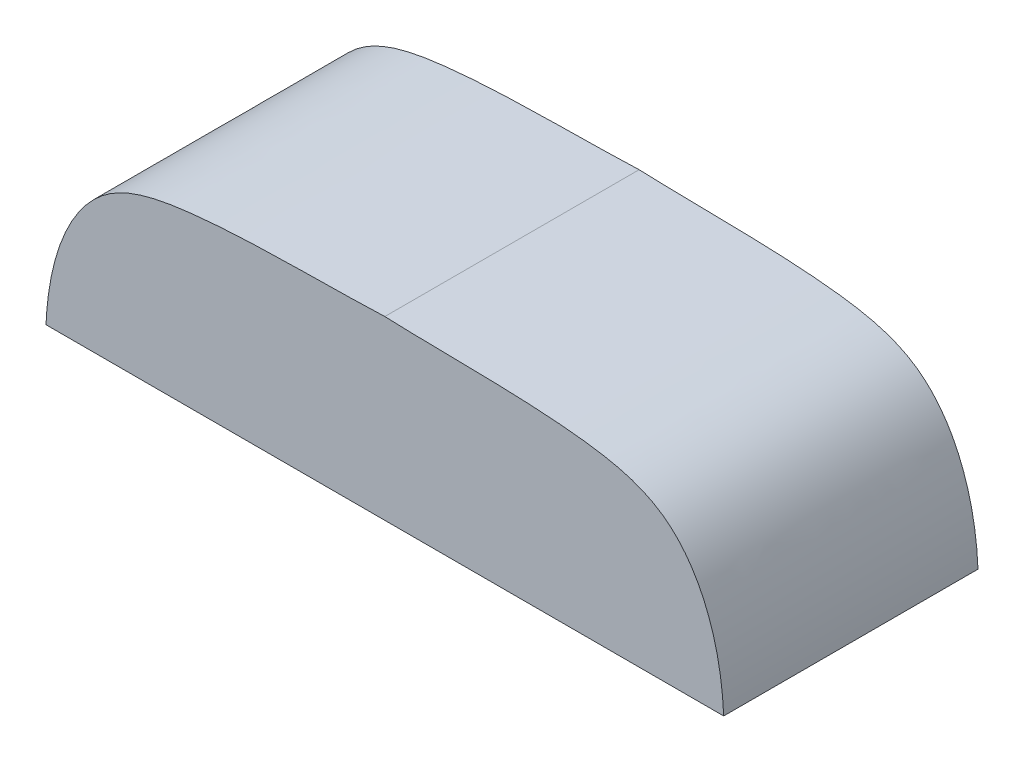
SolidWorks part; units mm, degrees
ref_plane "Front Plane" through (0, 0, 0) normal (0, 0, 1) x (1, 0, 0)
ref_plane "Top Plane" through (0, 0, 0) normal (0, 1, 0) x (1, 0, 0)
ref_plane "Right Plane" through (0, 0, 0) normal (1, 0, 0) x (0, 0, -1)
sketch "Sketch1" plane through (0, 0, 0) normal (0, 0, 1) x (1, 0, 0)
  line L2 (0, 265.0008) -> (0, -43.3016) construction
  line L3 (0, 55.9438) -> (-338.4201, 55.9438)
  line L4 (0, 55.9438) -> (338.4201, 55.9438)
  spline S0 degree 3 poles (0, 232.2583) (56.542, 229.7411) (174.4852, 232.8745) (302.7669, 203.9039) (335.8263, 117.8615) (338.4201, 55.9438) knots 0 0 0 0 0.225226 0.33784 0.524743 0.524743 0.524743 0.524743
  spline S1 degree 3 poles (0, 232.2583) (-56.542, 229.7411) (-174.4852, 232.8745) (-302.7669, 203.9039) (-335.8263, 117.8615) (-338.4201, 55.9438) knots 0 0 0 0 0.225226 0.33784 0.524743 0.524743 0.524743 0.524743
  point P2 (0, 0)
  point P3 (-338.4201, 55.9438)
  point P7 (0, 0)
  point P8 (0, 0.0638)
  point P12 (-278.928, 198.1798)
  point P19 (0, 0)
  point P20 (0, 55.9438)
  dimension "D2" = 55.88
extrude "Boss-Extrude1" add sketch "Sketch1" along normal blind 127 and the other way blind 127
